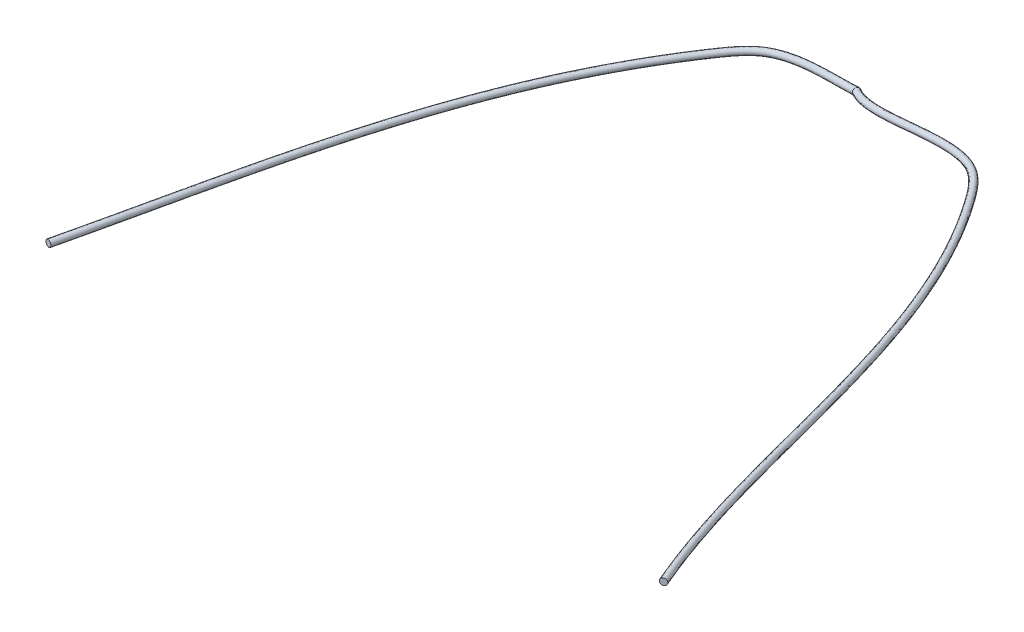
SolidWorks part; units mm, degrees
ref_plane "Front Plane" through (0, 0, 0) normal (0, 0, 1) x (1, 0, 0)
ref_plane "Top Plane" through (0, 0, 0) normal (0, 1, 0) x (1, 0, 0)
ref_plane "Right Plane" through (0, 0, 0) normal (1, 0, 0) x (0, 0, -1)
ref_plane "Plane1" through (0, 20.5189, 0) normal (0, 1, 0) x (1, 0, 0)
sketch "Sketch56" plane through (0, 20.5189, 0) normal (0, 1, 0) x (1, 0, 0)
  arc A2 (-15.6293, 16.1485) -> (-16.2695, 13.0158) centre (-6.278, 12.6057) ccw construction
  arc A3 (8.1975, 54.6974) -> (-0.6338, 48.7338) centre (8.5177, 44.7026) ccw construction
  spline S0 degree 3 poles (15.4215, 55.0341) (11.887, 54.7752) (4.1842, 55.6659) (-15.5818, 28.1026) (-19.8335, -0.4538) (-25.9685, -26.4025) knots 0 0 0 0 0.128648 0.183358 1 1 1 1
sketch "Sketch19" plane through (0, 20.5189, 0) normal (0, 1, 0) x (1, 0, 0)
  arc A2 (53.7305, 13.0158) -> (53.1636, 15.9824) centre (43.7374, 12.6437) ccw construction
  arc A3 (28.8375, 54.6974) -> (26.0834, 51.7075) centre (29.0834, 51.7075) ccw construction
  arc A4 (38.6757, 48.8215) -> (30.4819, 54.6974) centre (29.546, 44.7413) ccw construction
  spline S0 degree 3 poles (15.4215, 55.0341) (19.8391, 52.3823) (31.912, 57.8699) (54.1114, 29.1015) (54.993, -0.0858) (65.3672, -24.2196) knots 0 0 0 0 0.18384 0.242509 1 1 1 1
sweep "Sweep2" add path "Sketch19" circular profile diameter 1 parameters "D3"=1
sweep "Sweep3" add path "Sketch56" circular profile diameter 1 parameters "D3"=1
